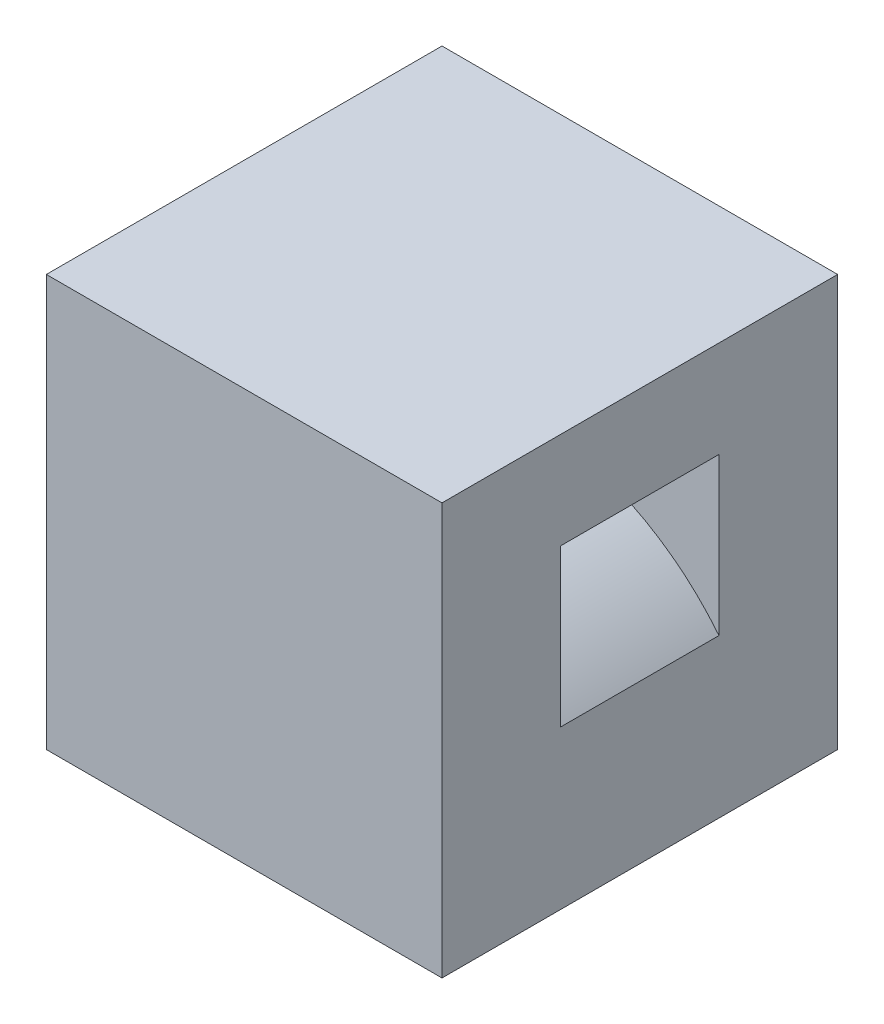
SolidWorks part; units mm, degrees
ref_plane "Front" through (0, 0, 0) normal (0, 0, 1) x (1, 0, 0)
ref_plane "Top" through (0, 0, 0) normal (0, 1, 0) x (1, 0, 0)
ref_plane "Right" through (0, 0, 0) normal (1, 0, 0) x (0, 0, -1)
sketch "Sketch1" plane through (0, 0, 0) normal (0, 0, 1) x (1, 0, 0)
  line L1 (-15.875, -16.51) -> (15.875, -16.51)
  line L2 (-15.875, -16.51) -> (-15.875, 16.51)
  line L3 (-15.875, 16.51) -> (15.875, 16.51)
  line L4 (15.875, -16.51) -> (15.875, 16.51)
  line L5 (-15.875, -16.51) -> (15.875, 16.51) construction
  line L6 (-15.875, 16.51) -> (15.875, -16.51) construction
  line L7 (-12.7, -16.51) -> (12.7, -16.51)
  line L8 (-12.7, -16.51) -> (-12.7, -3.81)
  line L9 (-12.7, -3.81) -> (12.7, -3.81)
  line L10 (12.7, -16.51) -> (12.7, -3.81)
  arc A0 (-15.875, -3.8259) -> (15.875, -3.8259) centre (0, -16.51) cw
  arc A1 (-15.875, 8.7627) -> (15.875, 8.7627) centre (0, -16.51) cw
  arc A2 (-23.3164, 2.1198) -> (23.3164, 2.1198) centre (0, -16.51) cw construction
  point P0 (0, 0)
  point P21 (0, 13.335)
  dimension "D5" = 20.32
  dimension "D1" = 25.4
  dimension "D2" = 12.7
  dimension "D3" = 3.175
  dimension "D4" = 3.175
  dimension "D7" = 3.175
  dimension "D6" = 9.525
extrude "Boss-Extrude1" add sketch "Sketch1" along normal blind 31.75 contours L2 L3 L4 L1
extrude "Cut-Extrude1" cut sketch "Sketch1<3>" along normal blind 25.4 from offset 3.175 contours L1 L10 L9 L8 region at (0, -10.16, 0)
sketch "Sketch1<3>" plane through (0, 0, 0) normal (0, 0, 1) x (1, 0, 0) same geometry as "Sketch1"
extrude "Cut-Extrude2" cut sketch "Sketch1<4>" along normal blind 12.7 from offset 9.525 contours A1 L2 A0 L4 region at (0, 6.5334, 0)
sketch "Sketch1<4>" plane through (0, 0, 0) normal (0, 0, 1) x (1, 0, 0) same geometry as "Sketch1"
equation "\"D4@Sketch1\"=\"D3@Sketch1\""
